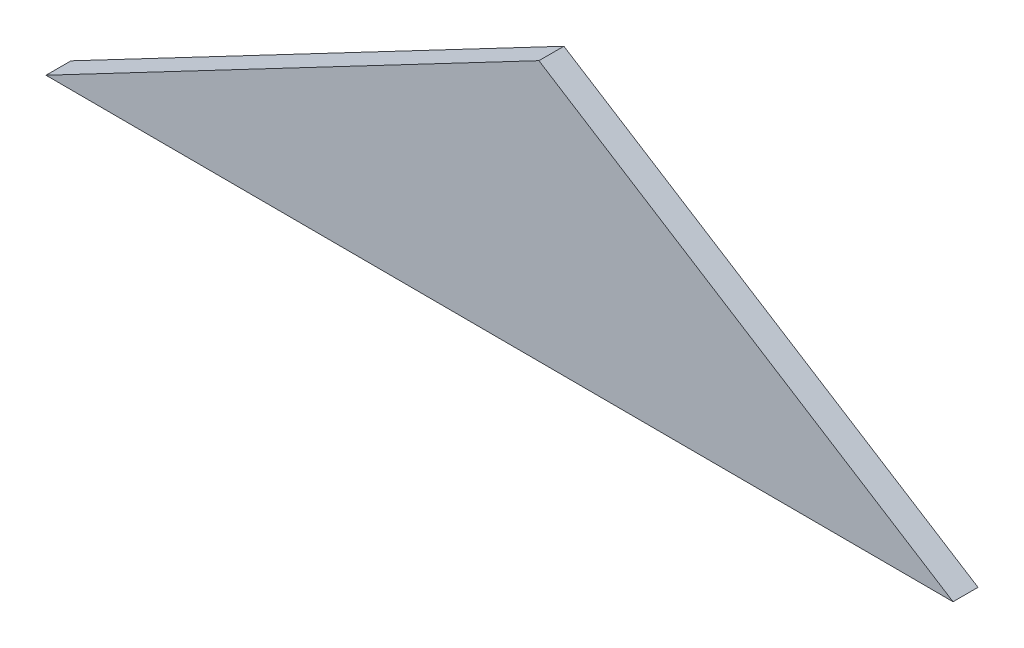
SolidWorks part; units mm, degrees
ref_plane "Front" through (0, 0, 0) normal (0, 0, 1) x (1, 0, 0)
ref_plane "Top" through (0, 0, 0) normal (0, 1, 0) x (1, 0, 0)
ref_plane "Right" through (0, 0, 0) normal (1, 0, 0) x (0, 0, -1)
sketch "Sketch1" plane through (0, 0, 0) normal (0, 0, 1) x (1, 0, 0)
  line L0 (-125.9664, -6.0666) -> (-27.224, 45.8327)
  line L1 (-27.224, 45.8327) -> (55.7322, -6.5563)
  line L2 (55.7322, -6.5563) -> (-125.9664, -6.0666)
  dimension "D1" = 120
extrude "Boss-Extrude1" add sketch "Sketch1" along normal blind 5
